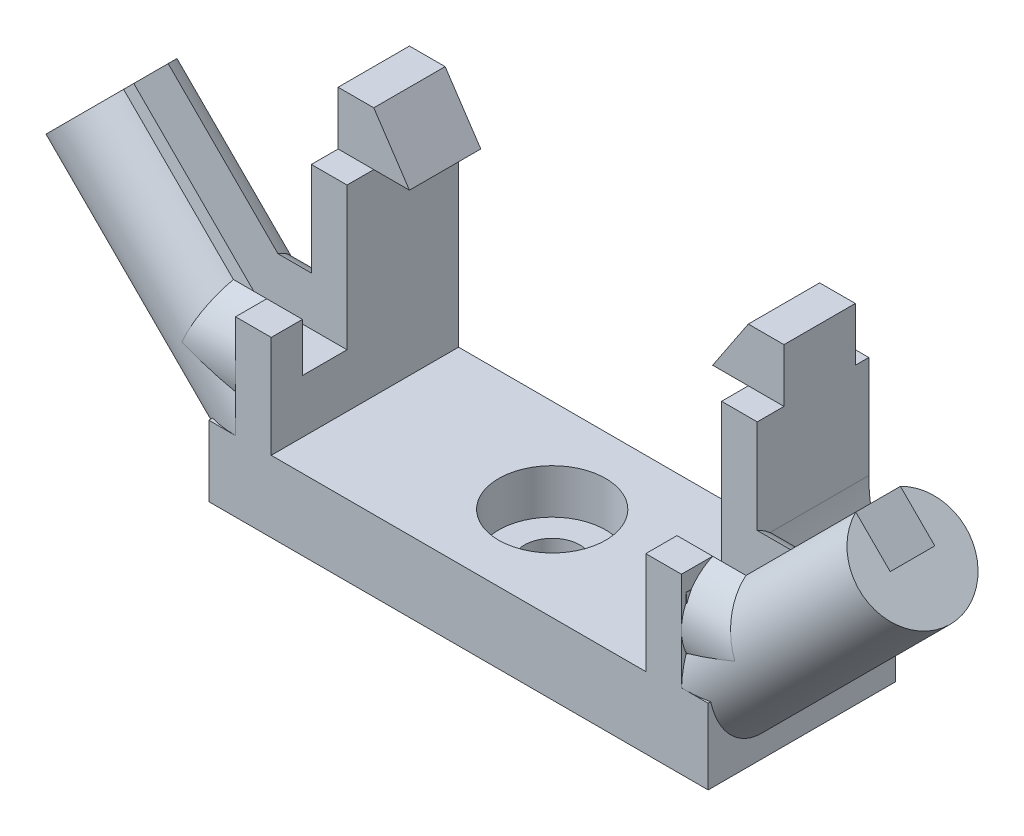
SolidWorks part; units mm, degrees
ref_plane "Front Plane" through (0, 0, 0) normal (0, 0, 1) x (1, 0, 0)
ref_plane "Top Plane" through (0, 0, 0) normal (0, 1, 0) x (1, 0, 0)
ref_plane "Right Plane" through (0, 0, 0) normal (1, 0, 0) x (0, 0, -1)
sketch "Sketch1" plane through (0, 0, 0) normal (0, 1, 0) x (1, 0, 0)
  line L0 (0, -44.7868) -> (0, 44.7868) construction
  line L1 (-14, 7.5) -> (14, 7.5)
  line L2 (-14, 7.5) -> (-14, -7.5)
  line L3 (-14, -7.5) -> (14, -7.5)
  line L4 (14, 7.5) -> (14, -7.5)
  line L5 (-44.2539, 0) -> (44.2539, 0) construction
  dimension "D1" = 15
  dimension "D2" = 28
  dimension "D3" = 14
  dimension "D4" = 7.5
extrude "Boss-Extrude1" add sketch "Sketch1" along normal blind 4
sketch "Sketch2" plane through (0, 0, 0) normal (0, 0, 1) x (1, 0, 0)
  line L0 (10.5, 4) -> (10.5, 18)
  line L1 (-14, 4) -> (14, 4) construction
  line L2 (10.5, 18) -> (12.5, 18)
  line L3 (12.5, 18) -> (12.5, 4)
  line L4 (12.5, 4) -> (10.5, 4)
  line L6 (-12.5, 4) -> (-12.5, 18)
  line L7 (-12.5, 18) -> (-10.5, 18)
  line L8 (-10.5, 18) -> (-10.5, 4)
  line L9 (-10.5, 4) -> (-12.5, 4)
  line L10 (0, -44.7868) -> (0, 44.7868) construction
  line L11 (-10.5, 18) -> (-8.5, 15)
  line L12 (-8.5, 15) -> (-10.5, 15)
  line L13 (10.5, 18) -> (8.5, 15)
  line L14 (8.5, 15) -> (10.5, 15)
  line L15 (-10.5, 18) -> (-10.5, 15)
  line L16 (10.5, 15) -> (10.5, 18)
  dimension "D1" = 21
  dimension "D2" = 14
  dimension "D3" = 10.5
  dimension "D4" = 2
  dimension "D5" = 3
  dimension "D6" = 2
extrude "Boss-Extrude2" add sketch "Sketch2" along normal mid plane 4 contours L9 L8 L7 L6 | L12 L11 L8 | L13 L14 L0 | L4 L3 L2 L0 region at (11.5, 11, 0) region at (9.8333, 16, 0) region at (-11.5, 11, 0) region at (-9.8333, 16, 0)
sketch "Sketch3" plane through (0, 0, 0) normal (0, 0, 1) x (1, 0, 0)
  line L0 (-12.5, 4) -> (-12.5, 18) construction
  line L1 (-12.5, 15) -> (-10.5, 15)
  line L2 (-12.5, 15) -> (-12.5, 4)
  line L3 (-12.5, 4) -> (-10.5, 4)
  line L4 (-10.5, 15) -> (-10.5, 4)
  line L5 (10.5, 4) -> (10.5, 15) construction
  line L6 (10.5, 15) -> (12.5, 15)
  line L7 (10.5, 15) -> (10.5, 4)
  line L8 (10.5, 4) -> (12.5, 4)
  line L9 (12.5, 15) -> (12.5, 4)
  dimension "D1" = 11
extrude "Boss-Extrude3" add sketch "Sketch3" along normal mid plane 15
fillet "Fillet1" radius 10 2 edges at (12.5, 4, 0) (-12.5, 4, 0)
ref_plane "Plane1" through (0, 0, 5) normal (0, 0, 1) x (1, 0, 0)
sketch "Sketch11" plane through (0, 4, 0) normal (0, 1, 0) x (1, 0, 0)
  circle A0 centre (0, 0) radius 1.55
  point P3 (0, 0)
  dimension "D1" = 3.1
extrude "Cut-Extrude3" [suppressed] cut sketch "Sketch11" against normal up to surface (4 mm away)
sketch "Sketch12" plane through (0, 4, 0) normal (0, 1, 0) x (1, 0, 0)
  circle A0 centre (0, 0) radius 3
  point P3 (0, 0)
  dimension "D1" = 6
extrude "Cut-Extrude4" [suppressed] cut sketch "Sketch12" against normal blind 2.5
sketch "Sketch13" plane through (-10.5, 0, 0) normal (1, 0, 0) x (0, 0, -1)
  line L0 (-7.5, 15) -> (-2, 15) construction
  line L1 (-3.5, 15) -> (-6, 15)
  line L2 (-3.5, 15) -> (-3.5, 7)
  line L3 (-3.5, 7) -> (-6, 7)
  line L5 (7.5, 4) -> (-7.5, 4) construction
  line L7 (-6, 7) -> (-6, 8.7184)
  line L8 (-6, 8.7184) -> (-7.5, 8.7184)
  line L9 (-7.5, 9.2678) -> (-7.5, 4) construction
  line L10 (-7.5, 8.7184) -> (-7.5, 15)
  line L11 (-7.5, 15) -> (-6, 15)
  dimension "D1" = 3
  dimension "D2" = 2.5
  dimension "D3" = 1.5
extrude "Cut-Extrude5" cut sketch "Sketch13" against normal up to surface and the other way up to surface up to face at (-13.0662, 6.5816, 0) other way up to face at (13.0662, 6.5816, 0)
sketch "Sketch14" plane through (-10.5, 0, 0) normal (1, 0, 0) x (0, 0, -1)
  line L0 (-3.5, 7) -> (-6, 7) construction
  line L1 (-6, 7) -> (-6, 8.7184) construction
  line L2 (-3.5, 9.2678) -> (-3.5, 7) construction
  line L3 (-3.5, 9.7272) -> (-3.5, 7)
  line L4 (-3.5, 7) -> (-6, 7)
  line L5 (-6, 7) -> (-6, 9.7272)
  arc A0 (-6, 9.7272) -> (-3.5, 9.7272) centre (-4.75, 7) ccw
  dimension "D1" = 3
extrude "Boss-Extrude4" add sketch "Sketch14" against normal blind 5
ref_plane "Plane4" through (0, 14, 0) normal (0, 1, 0) x (1, 0, 0)
sketch "Sketch17" plane through (0, 0, 5) normal (0, 0, 1) x (1, 0, 0)
  line L0 (-22.4113, 14) -> (-11.5172, 3.1059)
  line L1 (55, 14) -> (-55, 14) construction
  line L4 (0, -44.7868) -> (0, 44.7868) construction
  dimension "D1" = 45
sketch "Sketch18" plane through (-15.5, 0, 0) normal (-1, 0, 0) x (0, 0, 1)
  line L1 (3.5, 9.7272) -> (3.5, 7)
  line L2 (3.5, 7) -> (6, 7)
  line L3 (6, 7) -> (6, 9.7272)
  arc A2 (3.5, 9.7272) -> (6, 9.7272) centre (4.75, 7) ccw
  arc A3 (3.5, 9.7272) -> (6, 9.7272) centre (4.75, 7) ccw construction
sketch "Sketch20" plane through (0, 14, 0) normal (0, 1, 0) x (1, 0, 0)
  line L0 (-22.4113, -0.7886) -> (-22.4113, -8.452)
ref_plane "Plane5" through (-18.2057, 18.2057, 0) normal (0.7071, -0.7071, 0) x (-0.7071, -0.7071, 0)
sketch "Sketch21" plane through (-18.2057, 18.2057, 0) normal (0.7071, -0.7071, 0) x (-0.7071, -0.7071, 0)
  line L0 (6.0104, -6) -> (6.0104, -3.5)
  line L1 (6.0104, -3.5) -> (3.2832, -3.5)
  line L2 (4.082, -3.5) -> (1.9607, -3.5) construction
  line L3 (6.0104, -6) -> (3.2832, -6)
  line L4 (4.082, -6) -> (0.5465, -6) construction
  arc A0 (3.2832, -3.5) -> (3.2832, -6) centre (6.0104, -4.75) cw
  dimension "D2" = 3
  dimension "D1" = 2.5
sweep "Sweep3" add profiles "Sketch21" path "Sketch17"
mirror "Mirror1" about plane through (0, 0, 0) normal (1, 0, 0) of "Boss-Extrude4", "Sweep3"
sketch "Sketch22" plane through (0, 0, 7.5) normal (0, 0, 1) x (1, 0, 0)
  line L0 (10.5, 9.7272) -> (10.5, 8.7184) construction
  line L1 (10.5, 9.2228) -> (-10.5, 9.2228)
  line L2 (10.5, 9.2228) -> (10.5, 4)
  line L3 (10.5, 4) -> (-10.5, 4)
  line L4 (-10.5, 9.2228) -> (-10.5, 4)
extrude "Cut-Extrude6" cut sketch "Sketch22" against normal blind 15 and the other way blind 2
sketch "Sketch24" plane through (0, 0, 7.5) normal (0, 0, 1) x (1, 0, 0)
  line L0 (-10.5, 9.7272) -> (-12.5, 9.7272)
  line L1 (-12.5, 9.7272) -> (-12.5, 3.9567)
  line L2 (-12.5, 3.9567) -> (-14, 3.9567)
  line L3 (-14, 3.9567) -> (-14, 0)
  line L4 (55, 0) -> (-55, 0) construction
  line L5 (-14, 3.8044) -> (-14, 0) construction
  line L6 (-14, 0) -> (14, 0)
  line L7 (14, 3.8044) -> (14, 0) construction
  line L8 (14, 0) -> (14, 4.2121)
  line L9 (14, 4.2121) -> (12.5, 4.2121)
  line L10 (12.5, 4.2121) -> (12.5, 9.7272)
  line L11 (12.5, 9.7272) -> (10.5, 9.7272)
  line L12 (10.5, 9.7272) -> (10.5, 4)
  line L13 (10.5, 4) -> (-10.5, 4)
  line L14 (-10.5, 4) -> (-10.5, 9.7272)
extrude "Boss-Extrude6" add sketch "Sketch24" along normal through all and the other way up to surface (1.5 mm away) other way up to face at (-15.6422, 10.549, 6)
sketch "Sketch25" plane through (-12.5, 0, 0) normal (-1, 0, 0) x (0, 0, 1)
  line L1 (-7.5, 15) -> (-2.7546, 15)
  line L2 (-7.5, 15) -> (-7.5, 0)
  line L3 (-7.5, 0) -> (-2.7546, 0)
  line L4 (-2.7546, 15) -> (-2.7546, 0)
  line L5 (55, 0) -> (-55, 0) construction
  point P5 (-2.7546, 0)
  point P7 (0, 0)
  point P8 (0, 0)
extrude "Cut-Extrude7" cut sketch "Sketch25" against normal up to surface and the other way up to surface up to face at (14, 2.2628, 1.6842) other way up to face at (-14, 2.1987, 1.663)
sketch "Sketch26" plane through (0, 4, 0) normal (0, 1, 0) x (1, 0, 0)
  line L0 (0, -44.7868) -> (0, 44.7868) construction
  line L1 (-10.5, 2.7546) -> (10.5, 2.7546) construction
  circle A0 centre (0, -2.4954) radius 1.55
  dimension "D1" = 3.1
  dimension "D2" = 5.25
extrude "Cut-Extrude8" cut sketch "Sketch26" against normal up to surface (4 mm away) up to face at (0, 0, 2.4977)
sketch "Sketch27" plane through (0, 4, 0) normal (0, 1, 0) x (1, 0, 0)
  circle A0 centre (0, -2.4954) radius 3
  dimension "D1" = 6
extrude "Cut-Extrude9" cut sketch "Sketch27" against normal blind 2.5
equation "\"wid\"=28"
equation "\"D2@Sketch1\"=\"wid\""
equation "\"D3@Sketch1\"=\"wid\"/2"
equation "\"len\"=15"
equation "\"D1@Sketch1\"=\"len\""
equation "\"D4@Sketch1\"=\"len\"/2"
